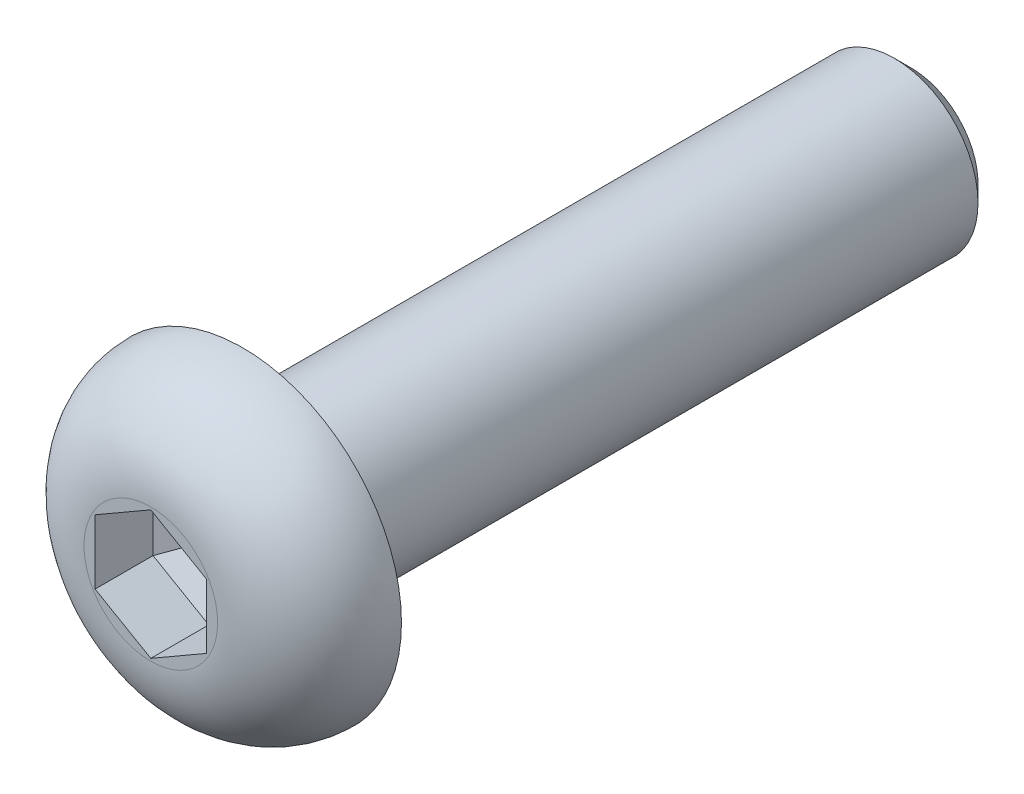
SolidWorks part; units mm, degrees
ref_plane "前视基准面" through (0, 0, 0) normal (0, 0, 1) x (1, 0, 0)
ref_plane "上视基准面" through (0, 0, 0) normal (0, 1, 0) x (1, 0, 0)
ref_plane "右视基准面" through (0, 0, 0) normal (1, 0, 0) x (0, 0, -1)
sketch "草图1" plane through (0, 0, 0) normal (0, 0, 1) x (1, 0, 0)
  circle A0 centre (0, 0) radius 2.85
  dimension "dk" = 5.7
extrude "凸台-拉伸1" add sketch "草图1" along normal blind 1.65
ref_axis "基准轴1" through (0, 0, 1.65) along (0, 0, -1)
fillet "圆角1" radius 1.65 1 edges at (2.85, 0, 1.65)
sketch "草图3" plane through (0, 0, 0) normal (0, 0, -1) x (-1, 0, 0)
  circle A0 centre (0, 0) radius 1.5
  dimension "d" = 3
extrude "凸台-拉伸3" add sketch "草图3" along normal blind 12
cosmetic thread "装饰螺纹线1" parameters "b"=11.9, "D2"=2.459
sketch "草图4" plane through (0, 0, 1.65) normal (0, 0, 1) x (1, 0, 0)
  line L1 (1, 0.5774) -> (0, 1.1547)
  line L2 (0, 1.1547) -> (-1, 0.5774)
  line L3 (-1, 0.5774) -> (-1, -0.5774)
  line L4 (-1, -0.5774) -> (0, -1.1547)
  line L5 (0, -1.1547) -> (1, -0.5774)
  line L6 (1, -0.5774) -> (1, 0.5774)
  circle A0 centre (0, 0) radius 1 construction
  dimension "s" = 2
extrude "切除-拉伸1" cut sketch "草图4" against normal blind 1.6164
chamfer "倒角2" distance 0.3 angle 45 1 edges at (-1.5, 0, -12)
chamfer "倒角3" distance 0.5764 angle 60 6 edges at (-0.5, -0.866, 0.0336) (-1, 0, 0.0336) (-0.5, 0.866, 0.0336) (0.5, 0.866, 0.0336) (0.5, -0.866, 0.0336) (1, 0, 0.0336) first distance on face at (-0.5, -0.866, 0.8418) first distance on face at (-1, 0, 0.8418) first distance on face at (-0.5, 0.866, 0.8418) first distance on face at (0.5, 0.866, 0.8418) first distance on face at (0.5, -0.866, 0.8418) first distance on face at (1, 0, 0.8418)
fillet "圆角2" radius 0.1 1 edges at (1.5, 0, 0)
ref_plane "基准面1" through (0, 0, 0) normal (0, 0, -1) x (-1, 0, 0)
equation "\"D1@倒角3\"=\"s@草图4\" /3.47"
equation "\"D1@倒角2\"= \"d@草图3\" / 10"
equation "\"D1@圆角1\"=\"k@凸台-拉伸1\""
